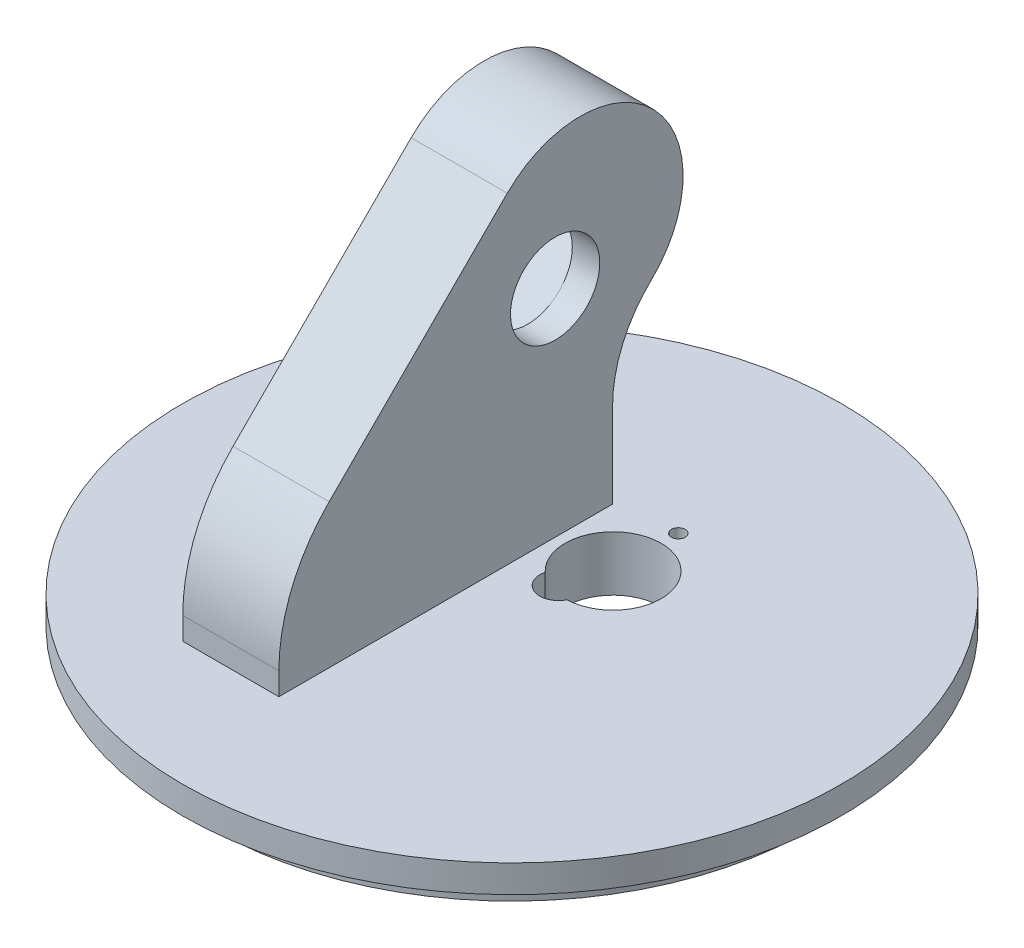
SolidWorks part; units mm, degrees
ref_plane "Front Plane" through (0, 0, 0) normal (0, 0, 1) x (1, 0, 0)
ref_plane "Top Plane" through (0, 0, 0) normal (0, 1, 0) x (1, 0, 0)
ref_plane "Right Plane" through (0, 0, 0) normal (1, 0, 0) x (0, 0, -1)
sketch "Sketch2" plane through (0, 0, 0) normal (0, 1, 0) x (1, 0, 0)
  circle A0 centre (0, 0) radius 48
  dimension "D1" = 96
extrude "Boss-Extrude1" add sketch "Sketch2" along normal blind 4
ref_plane "Plane1" through (-4, 0, 0) normal (1, 0, 0) x (0, 0, -1)
sketch "Sketch7" plane through (-4, 0, 0) normal (1, 0, 0) x (0, 0, -1)
  line L0 (18.6521, 16.3561) -> (18.6521, 4)
  line L5 (48, 4) -> (-48, 4) construction
  line L6 (-22.6311, 24.9401) -> (3.3119, 50.8831)
  line L7 (-43.5609, 4) -> (18.6521, 4)
  line L11 (-29.9535, 4) -> (-29.9535, 7.2624)
  arc A4 (24.252, 29.4036) -> (3.3119, 50.8831) centre (13.9185, 40.2765) ccw
  arc A5 (24.252, 29.4036) -> (18.6521, 16.3561) centre (36.6521, 16.3561) ccw
  arc A6 (-22.6311, 24.9401) -> (-29.9535, 7.2624) centre (-4.9535, 7.2624) ccw
  dimension "D1" = 25
  dimension "D4" = 30
  dimension "D3" = 18
  dimension "D5" = 45
extrude "Boss-Extrude2" add sketch "Sketch7" against normal blind 14 contours A5 A4 L6 L7 L0 | A4 | A4 | A4 | L6 A6 L7 region at (-4, 26.0967, -1.8639)
ref_plane "Plane2" through (-6, 0, 0) normal (1, 0, 0) x (0, 0, -1)
sketch "Sketch31" plane through (-18, 10.4618, -5.3595) normal (-1, 0, 0) x (0, 0, 1)
  line L0 (-5.4155, 34.0546) -> (11.7496, 18.7458)
  line L1 (11.7496, 18.7458) -> (3.0968, 9.0438)
  line L2 (3.0968, 9.0438) -> (-14.0683, 24.3526)
  line L3 (-14.0683, 24.3526) -> (-5.4155, 34.0546)
  circle A0 centre (-4.9225, 24.9054) radius 6.5
  dimension "D1" = 6.5
extrude "Cut-Extrude18" cut sketch "Sketch31" against normal through all contours A0
extrude "Cut-Extrude19" cut sketch "Sketch31<3>" against normal blind 10 contours L0 L1 L2 L3
sketch "Sketch31<3>" plane through (-18, 10.4618, -5.3595) normal (-1, 0, 0) x (0, 0, 1) same geometry as "Sketch31"
sketch "Sketch32" plane through (-18, 0, 0) normal (-1, 0, 0) x (0, 0, 1)
  line L0 (6.3901, 29.2076) -> (-2.2627, 19.5056) construction
  circle A0 centre (-17.0806, 41.2645) radius 1
  circle A1 centre (3.9294, 22.6926) radius 1
  arc A3 (-14.6084, 40.2182) -> (-15.5944, 39.1126) centre (-10.282, 35.3672) ccw construction
  dimension "D1" = 2.5
  dimension "D2" = 2.5
extrude "Cut-Extrude20" cut sketch "Sketch32" against normal blind 4.5
sketch "Sketch33" plane through (0, 0, 0) normal (0, -1, 0) x (1, 0, 0)
  circle A0 centre (0, 0) radius 43.5
extrude "Boss-Extrude3" add sketch "Sketch33" along normal blind 4
sketch "Sketch35" plane through (-3.1928, 4, -10.2509) normal (0, 1, 0) x (1, 0, 0)
  circle A0 centre (7.6655, 0) radius 7
extrude "Cut-Extrude22" cut sketch "Sketch35" against normal through all
sketch "Sketch36" plane through (0, 4, 0) normal (0, 1, 0) x (1, 0, 0)
  circle A0 centre (2.3101, 4.4441) radius 2.7018
extrude "Cut-Extrude24" cut sketch "Sketch36" against normal through all contours A0
sketch "Sketch37" plane through (0, 4, 0) normal (0, 1, 0) x (1, 0, 0)
  circle A0 centre (4.4727, 19.7509) radius 1
  arc A1 (4.7366, 3.2559) -> (-0.3026, 5.1326) centre (4.4727, 10.2509) ccw construction
  dimension "D1" = 2.5
extrude "Cut-Extrude25" cut sketch "Sketch37" against normal blind 4.5
